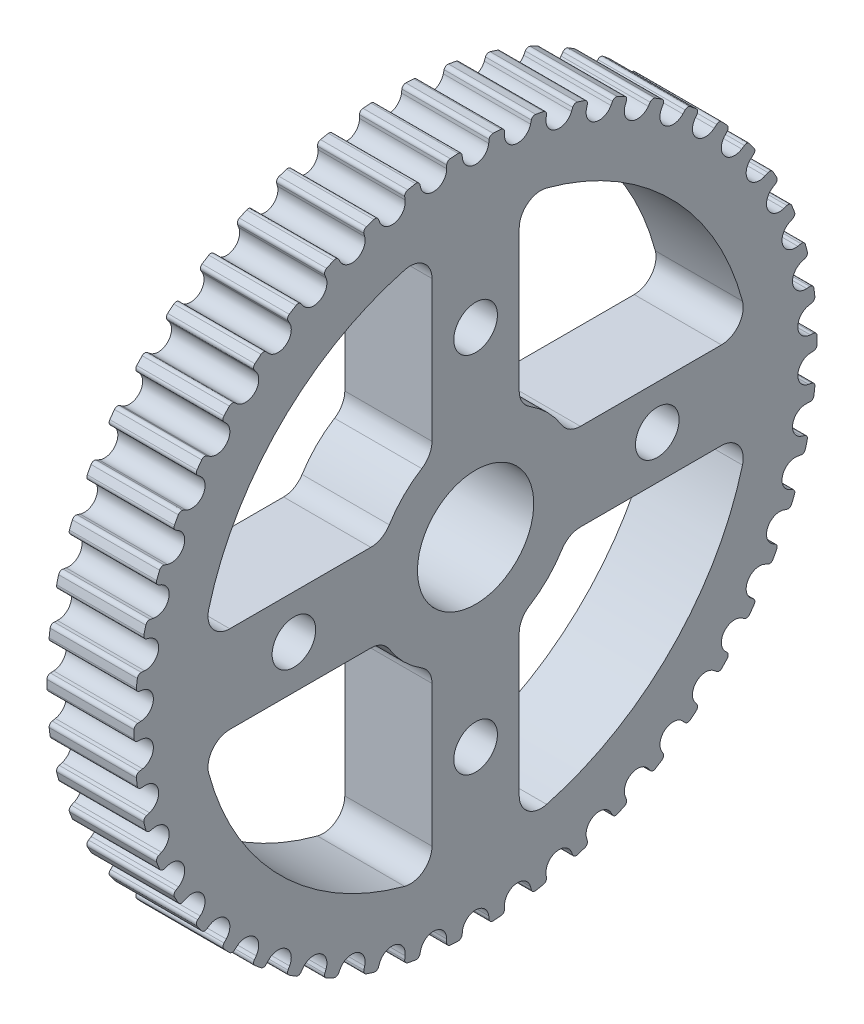
SolidWorks part; units mm, degrees
material "Thornel Mat VMA"
ref_plane "前视基准面" through (0, 0, 0) normal (0, 0, 1) x (1, 0, 0)
ref_plane "上视基准面" through (0, 0, 0) normal (0, 1, 0) x (1, 0, 0)
ref_plane "右视基准面" through (0, 0, 0) normal (1, 0, 0) x (0, 0, -1)
sketch "草图1" plane through (0, 0, 0) normal (0, 0, 1) x (1, 0, 0)
  line L0 (0, 0) -> (64.8368, 0) construction
  line L1 (0, 5.6156) -> (0, 23.494)
  line L2 (0, 23.494) -> (6, 23.494)
  line L3 (6, 23.494) -> (6, 11.2312)
  line L4 (6, 11.2312) -> (7.2, 11.2312)
  line L5 (7.2, 11.2312) -> (7.2, 5.6156)
  line L6 (7.2, 5.6156) -> (0, 5.6156)
  dimension "L" = 7.2
  dimension "B" = 6
  dimension "d" = 11.2312
  dimension "d1" = 22.4624
  dimension "da" = 46.988
revolve "旋转1" add sketch "草图1" angle 360 about L0
chamfer "倒角1" distance 1 angle 45 2 edges at (7.2, 0, 5.6156) (0, 0, 5.6156)
sketch "草图4" plane through (0, 0, 0) normal (-1, 0, 0) x (0, 0, 1)
  line L1 (-2, 5.2474) -> (2, 5.2474)
  line L2 (-2, 5.2474) -> (-2, 7.0474)
  line L3 (-2, 7.0474) -> (2, 7.0474)
  line L4 (2, 5.2474) -> (2, 7.0474)
  circle A0 centre (0, 0) radius 5.6156 construction
  dimension "键槽宽度" = 4
  dimension "t1" = 1.8
extrude "切除-拉伸1" cut sketch "草图4" against normal through all
ref_axis "基准轴1" through (-0.3, 0, 0) along (1, 0, 0)
sketch "草图6" plane through (0, 0, 0) normal (1, 0, 0) x (0, 0, -1)
  line L0 (0, 0) -> (0, 30.6512) construction
  line L1 (0.9305, 23.2353) -> (0.9032, 23.0131)
  line L2 (1.4614, 23.4485) -> (1.6581, 25.0501)
  line L3 (-1.4614, 23.4485) -> (-1.6581, 25.0501)
  line L4 (-0.9305, 23.2353) -> (-0.9032, 23.0131)
  circle A0 centre (0, 0) radius 23.494 construction
  circle A1 centre (0, 0) radius 22.214 construction
  arc A2 (-0.9032, 23.0131) -> (0.9032, 23.0131) centre (0, 23.124) ccw
  arc A3 (1.6581, 25.0501) -> (-1.6581, 25.0501) centre (0, 0) ccw
  arc A4 (0.9305, 23.2353) -> (1.2019, 23.4632) centre (1.1886, 23.2036) cw
  arc A5 (1.2019, 23.4632) -> (1.4614, 23.4485) centre (0, 0) cw
  arc A6 (-1.2019, 23.4632) -> (-1.4614, 23.4485) centre (0, 0) ccw
  arc A7 (-0.9305, 23.2353) -> (-1.2019, 23.4632) centre (-1.1886, 23.2036) ccw
  point P7 (0, 1.9)
  point P8 (0, 29.3712)
  point P15 (0.9599, 23.4744)
  dimension "D1" = 44.428
  dimension "ra" = 0.26
  dimension "rf" = 0.91
  dimension "hg" = 1.28
  dimension "D3" = 0.26
  dimension "D4" = 1.6136
  dimension "angle" = 14
  dimension "bw" = 1.9
extrude "切除-拉伸2" cut sketch "草图6" along normal up to next
pattern_circular "阵列(圆周)3" count 50 over 360 about axis through (-0.3, 0, 0) along (1, 0, 0) of "切除-拉伸2"
sketch "草图7" plane through (6, 0, 0) normal (1, 0, 0) x (0, 0, -1)
  circle A0 centre (0, 0) radius 14
  dimension "D1" = 28
extrude "切除-拉伸3" cut sketch "草图7" along normal blind 10
sketch "草图8" plane through (6, 0, 0) normal (1, 0, 0) x (0, 0, -1)
  circle A0 centre (0, 0) radius 7.3257
extrude "凸台-拉伸1" add sketch "草图8" against normal up to surface (6 mm away) up to face at (0, 3.4463, 0)
sketch "草图9" plane through (0, 0, 0) normal (-1, 0, 0) x (0, 0, 1)
  circle A0 centre (0, 0) radius 4
  dimension "D1" = 8
extrude "切除-拉伸4" cut sketch "草图9" against normal up to surface (6 mm away)
sketch "草图10" plane through (6, 0, 0) normal (1, 0, 0) x (0, 0, -1)
  circle A0 centre (0, 0) radius 12.5 construction
  circle A1 centre (0, 12.5) radius 1.5
  circle A2 centre (0, -12.5) radius 1.5
  circle A3 centre (12.5, 0) radius 1.5
  circle A4 centre (-12.5, 0) radius 1.5
  dimension "D1" = 25
  dimension "D2" = 3
extrude "切除-拉伸5" cut sketch "草图10" against normal up to next
sketch "草图11" plane through (6, 0, 0) normal (1, 0, 0) x (0, 0, -1)
  line L0 (0, 0) -> (0, 19) construction
  line L1 (0, 0) -> (0, -19) construction
  line L2 (3, 0) -> (3, -19)
  line L3 (3, 0) -> (3, 19)
  line L4 (-3, 0) -> (-3, -19)
  line L5 (-3, 0) -> (-3, 19)
  line L6 (-19, 0) -> (19, 0) construction
  line L7 (-19, -3) -> (19, -3)
  line L8 (-19, 3) -> (19, 3)
  circle A0 centre (0, 0) radius 19
  circle A1 centre (0, 0) radius 7
  circle A2 centre (0, 0) radius 4 construction
  dimension "D1" = 38
  dimension "D4" = 3
  dimension "D2" = 3
  dimension "D3" = 3
  dimension "D5" = 3
  dimension "D6" = 3
extrude "切除-拉伸6" cut sketch "草图11" against normal up to next contours A1 L5 A0 L8 | A1 L8 A0 L3 | A1 L2 A0 L7 | A1 L7 A0 L4 region at (6, -9.5765, -9.5765) region at (6, 9.5765, -9.5765) region at (6, -9.5765, 9.5765) region at (6, 9.5765, 9.5765)
fillet "圆角1" radius 1.5 16 edges at (3, -6.3246, 3) (3, -18.7617, 3) (3, -3, 18.7617) (3, -3, 6.3246) (3, 3, -18.7617) (3, 3, -6.3246) (3, 3, 6.3246) (3, 3, 18.7617) (3, 18.7617, 3) (3, 6.3246, 3) (3, -3, -6.3246) (3, -3, -18.7617) (3, -18.7617, -3) (3, -6.3246, -3) (3, 6.3246, -3) (3, 18.7617, -3)
equation "\"D1@草图6\" = \"da@草图1\"  - \"hg@草图6\" - \"hg@草图6\""
equation "\"D3@草图6\" = \"ra@草图6\""
